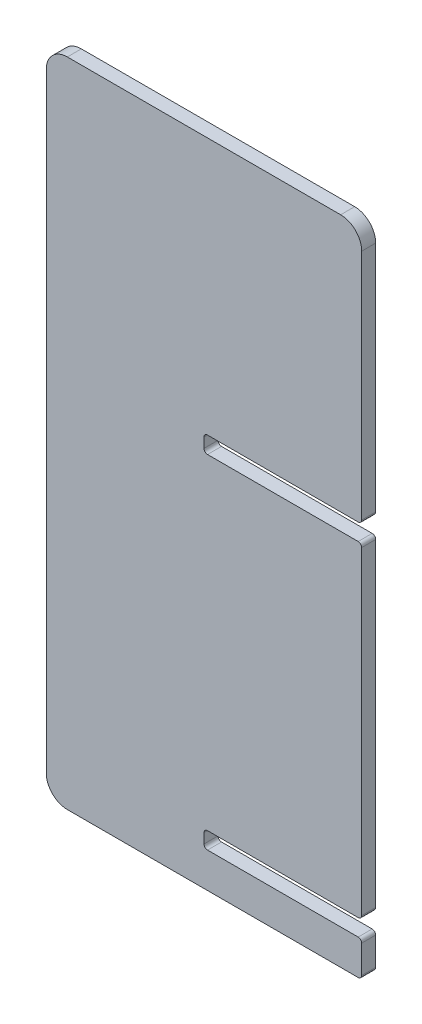
SolidWorks part; units mm, degrees
ref_plane "Alzado" through (0, 0, 0) normal (0, 0, 1) x (1, 0, 0)
ref_plane "Planta" through (0, 0, 0) normal (0, 1, 0) x (1, 0, 0)
ref_plane "Vista lateral" through (0, 0, 0) normal (1, 0, 0) x (0, 0, -1)
sketch "Croquis1" plane through (0, 0, 0) normal (0, 0, 1) x (1, 0, 0)
  line L1 (-22.5, 45) -> (22.5, 45)
  line L2 (-22.5, 45) -> (-22.5, -48)
  line L3 (-22.5, -48) -> (22.5, -48)
  line L4 (22.5, 45) -> (22.5, -48)
  dimension "D1" = 45
  dimension "D2" = 22.5
  dimension "D3" = 93
  dimension "D4" = 45
extrude "Saliente-Extruir1" add sketch "Croquis1" along normal blind 2 contours L2 L3 L4 L1
sketch "Croquis2" plane through (0, 0, 2) normal (0, 0, 1) x (1, 0, 0)
  line L0 (22.5, 45) -> (22.5, -48) construction
  line L1 (22.5, 8.2795) -> (0, 8.2795)
  line L2 (22.5, 8.2795) -> (22.5, 5.8795)
  line L3 (22.5, 5.8795) -> (0, 5.8795)
  line L4 (0, 8.2795) -> (0, 5.8795)
  dimension "D1" = 22.5
  dimension "D2" = 2.4
  dimension "D3" = 5.8795
extrude "Cortar-Extruir1" cut sketch "Croquis2" against normal up to surface (2 mm away) up to face at (0, -1.5, 0)
sketch "Croquis3" plane through (0, 0, 2) normal (0, 0, 1) x (1, 0, 0)
  line L0 (22.5, 5.8795) -> (22.5, -48) construction
  line L1 (22.5, -40.6) -> (0, -40.6)
  line L2 (22.5, -40.6) -> (22.5, -43)
  line L3 (22.5, -43) -> (0, -43)
  line L4 (0, -40.6) -> (0, -43)
  line L5 (-22.5, -48) -> (22.5, -48) construction
  dimension "D1" = 2.4
  dimension "D2" = 5
  dimension "D3" = 22.5
extrude "Cortar-Extruir2" cut sketch "Croquis3" against normal up to surface (2 mm away) up to face at (5.625, 2.7897, 0)
fillet "Redondeo1" radius 3 3 edges at (-22.5, -48, 1) (22.5, 45, 1) (-22.5, 45, 1)
fillet "Redondeo2" radius 0.5 9 edges at (22.5, 5.8795, 1) (22.5, 8.2795, 1) (0, 8.2795, 1) (0, 5.8795, 1) (22.5, -43, 1) (0, -43, 1) (0, -40.6, 1) (22.5, -40.6, 1) (22.5, -48, 1)
